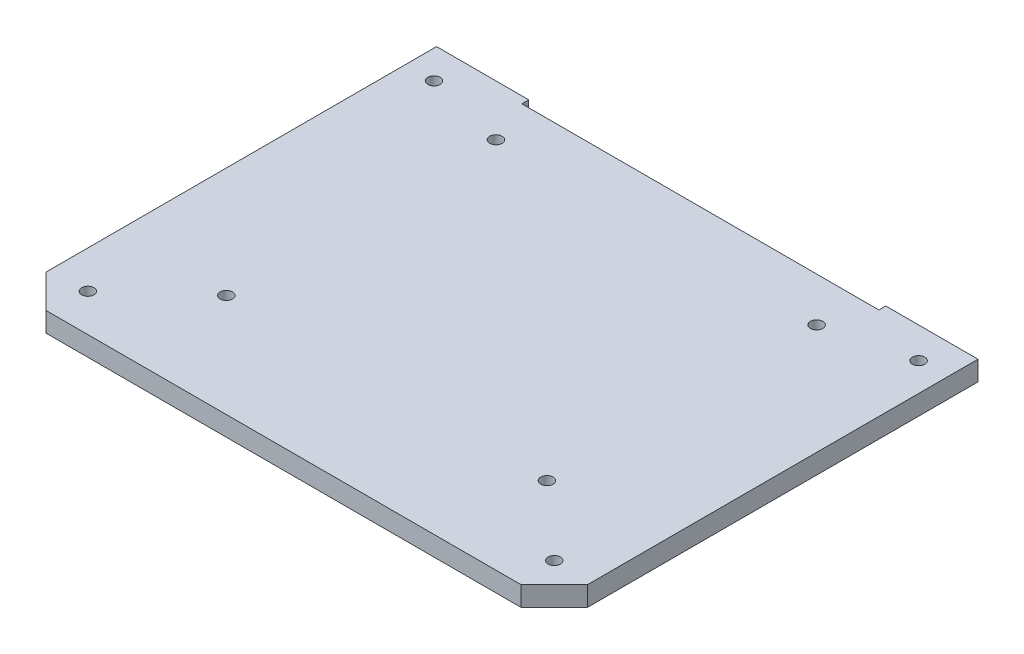
SolidWorks part; units mm, degrees
ref_plane "Front Plane" through (0, 0, 0) normal (0, 0, 1) x (1, 0, 0)
ref_plane "Top Plane" through (0, 0, 0) normal (0, 1, 0) x (1, 0, 0)
ref_plane "Right Plane" through (0, 0, 0) normal (1, 0, 0) x (0, 0, -1)
ref_plane "PZ26" through (0, 26, 0) normal (0, 1, 0) x (1, 0, 0)
sketch "Sketch1" plane through (0, 26, 0) normal (0, 1, 0) x (1, 0, 0)
  line L0 (-65.187, -126.3) -> (65.187, -126.3)
  line L1 (65.187, -126.3) -> (74.3, -117.187)
  line L2 (74.3, -117.187) -> (74.3, -11.9)
  line L3 (74.3, -11.9) -> (-74.3, -11.9)
  line L4 (-74.3, -11.9) -> (-74.3, -117.187)
  line L5 (-74.3, -117.187) -> (-65.187, -126.3)
extrude "Lid Plate" add sketch "Sketch1" along normal blind 2.4
ref_plane "PZ23" through (0, 23, 0) normal (0, 1, 0) x (1, 0, 0)
sketch "Sketch2" plane through (0, 23, 0) normal (0, 1, 0) x (1, 0, 0)
  line L0 (74.3, -11.9) -> (74.3, -117.187)
  line L1 (74.3, -117.187) -> (65.187, -126.3)
  line L2 (65.187, -126.3) -> (-65.187, -126.3)
  line L3 (-65.187, -126.3) -> (-74.3, -117.187)
  line L4 (-74.3, -117.187) -> (-74.3, -11.9)
  line L5 (-74.3, -11.9) -> (-72.7, -11.9)
  line L6 (-72.7, -11.9) -> (-72.7, -116.5243)
  line L7 (-72.7, -116.5243) -> (-64.5243, -124.7)
  line L8 (-64.5243, -124.7) -> (64.5243, -124.7)
  line L9 (64.5243, -124.7) -> (72.7, -116.5243)
  line L10 (72.7, -116.5243) -> (72.7, -11.9)
  line L11 (72.7, -11.9) -> (74.3, -11.9)
extrude "Drip Skirt" add sketch "Sketch2" along normal blind 3.01
sketch "Sketch3" plane through (0, 23, 0) normal (0, 1, 0) x (1, 0, 0)
  line L0 (-74.3, -11.9) -> (-49, -11.9)
  line L1 (-49, -11.9) -> (-49, -10)
  line L2 (-49, -10) -> (-74.3, -10)
  line L3 (-74.3, -10) -> (-74.3, -11.9)
extrude "Front Skirt L" add sketch "Sketch3" along normal blind 5.4
sketch "Sketch4" plane through (0, 23, 0) normal (0, 1, 0) x (1, 0, 0)
  line L0 (49, -11.9) -> (74.3, -11.9)
  line L1 (74.3, -11.9) -> (74.3, -10)
  line L2 (74.3, -10) -> (49, -10)
  line L3 (49, -10) -> (49, -11.9)
extrude "Front Skirt R" add sketch "Sketch4" along normal blind 5.4
ref_plane "PZ25" through (0, 25, 0) normal (0, 1, 0) x (1, 0, 0)
sketch "Sketch5" plane through (0, 25, 0) normal (0, 1, 0) x (1, 0, 0)
  circle A0 centre (-66.5, -18.5) radius 1.7
  circle A1 centre (66.5, -18.5) radius 1.7
  circle A2 centre (-64, -116) radius 1.7
  circle A3 centre (64, -116) radius 1.7
  circle A4 centre (-44, -24) radius 1.7
  circle A5 centre (-44, -98) radius 1.7
  circle A6 centre (44, -24) radius 1.7
  circle A7 centre (44, -98) radius 1.7
extrude "Screw Holes" cut sketch "Sketch5" along normal blind 4.4
equation "\"BOARD_REAR\" = 86.0"
equation "\"BOARD_FRONT\" = 41.0"
equation "\"BOARD_END\" = 22.0"
equation "\"BOARD_ANGLED\" = 30.0"
equation "\"BOARD_DEPTH\" = 41.8431"
equation "\"PCB_T\" = 1.6"
equation "\"ABOVE_PCB\" = 14.0"
equation "\"BELOW_PCB\" = 6.0"
equation "\"MID_PARTS_H\" = 9.0"
equation "\"BOARD_HOLE_PILOT\" = 1.6"
equation "\"J2_X\" = 19.0"
equation "\"DUPONT_DROP\" = 14.0"
equation "\"BEND_R\" = 5.0"
equation "\"BOARD_GAP\" = 3.0"
equation "\"TOF_FOV\" = 25.0"
equation "\"TOF_MARGIN_DEG\" = 5.0"
equation "\"TOF_WIN_MARGIN\" = 1.0"
equation "\"TOF_Z\" = 9.0"
equation "\"TOF_SIDE_BEARING\" = 90.0"
equation "\"TOF_CONE_LEN\" = 70.0"
equation "\"CAM_W\" = 29.2"
equation "\"CAM_H\" = 28.2"
equation "\"CAM_D\" = 12.35"
equation "\"CAM_FRONT_Y\" = 43.0"
equation "\"CAM_BOTTOM_Z\" = 17.0"
equation "\"CAM_LENS_UP\" = 11.6"
equation "\"CAM_LENS_OPEN\" = 9.6"
equation "\"CAM_HFOV\" = 53.5"
equation "\"CAM_VFOV\" = 41.41"
equation "\"CAM_FOV_MARGIN\" = 3.0"
equation "\"CAM_FIT\" = 0.3"
equation "\"RIBBON_W\" = 16.0"
equation "\"RIBBON_T\" = 0.3"
equation "\"RIBBON_LEN\" = 150.0"
equation "\"RIBBON_EXIT_Y\" = 35.0"
equation "\"WALL\" = 2.4"
equation "\"HEAD_X\" = 48.4"
equation "\"HEAD_REAR_Y\" = -11.9"
equation "\"CAM_FOAM\" = 2.8"
equation "\"HEAD_FRONT_Y\" = 48.2"
equation "\"HEAD_TOP_Z\" = 50.6"
equation "\"HEAD_BOT_Z\" = -28.4"
equation "\"HEAD_SPLIT_Z\" = -4.0"
equation "\"SKIRT_T\" = 1.2"
equation "\"SKIRT_H\" = 3.0"
equation "\"SKIRT_FIT\" = 0.3"
equation "\"VISOR\" = 7.8"
equation "\"VISOR_Z\" = 40.0"
equation "\"ROOF_SLOPE_Y\" = 40.0"
equation "\"ROOF_CHAMFER\" = 10.0"
equation "\"REAR_CHAMFER\" = 10.0"
equation "\"CORNER_CHAMFER\" = 6.0"
equation "\"LOWER_SIDE_FACET\" = 6.0"
equation "\"LIGHTBAR_DEPTH\" = 1.0"
equation "\"HOOD_Z\" = 14.0"
equation "\"HOOD_L\" = 6.0"
equation "\"SIDE_HOOD_L\" = 4.0"
equation "\"INSERT_M3_D\" = 4.0"
equation "\"INSERT_M3_L\" = 6.0"
equation "\"M3_CLEAR\" = 3.4"
equation "\"M2_PILOT\" = 1.6"
equation "\"M25_PILOT\" = 2.2"
equation "\"BOX_X\" = 72.4"
equation "\"BOX_FRONT_Y\" = -11.9"
equation "\"BOX_REAR_Y\" = -124.4"
equation "\"BOX_BOT_Z\" = -28.4"
equation "\"BOX_TOP_Z\" = 26.0"
equation "\"LID_T\" = 2.4"
equation "\"LID_SKIRT\" = 1.6"
equation "\"LID_TONGUE_H\" = 3.0"
equation "\"LID_FIT\" = 0.3"
equation "\"PI_STANDOFF\" = 8.0"
equation "\"BOX_REAR_CHAMFER\" = 8.0"
equation "\"BOX_REAR_FACET\" = 4.0"
equation "\"VENT_UPSTAND\" = 3.0"
equation "\"TUBE_D\" = 22.2"
equation "\"TUBE_LINER\" = 1.0"
equation "\"MOUNT_Y\" = -70.0"
equation "\"RAIL_W\" = 30.0"
equation "\"RAIL_W2\" = 38.0"
equation "\"RAIL_H\" = 6.0"
equation "\"SLIDE\" = 0.3"
equation "\"STOP_T\" = 6.0"
equation "\"CLAMP_W\" = 40.0"
equation "\"CLAMP_HALF\" = 20.0"
equation "\"CLAMP_DROP\" = 12.0"
equation "\"CAP_T\" = 12.0"
equation "\"CLAMP_BOLT_OFF\" = 16.6"
equation "\"M5_INSERT_D\" = 6.4"
equation "\"M5_CLEAR\" = 5.5"
equation "\"LOCK_D\" = 3.3"
equation "\"POD_TILT_DEG\" = 0.0"
equation "\"PRINT_LIMIT\" = 180.0"
equation "\"PI5_L\" = 85.0"
equation "\"PI5_W\" = 56.0"
equation "\"PI5_T\" = 1.6"
equation "\"PI5_USBC_BX\" = 11.2"
equation "\"PI5_ETH_BY\" = 10.2"
equation "\"PI5_PORT_OVERHANG\" = 3.0"
equation "\"PI5_FPC_H\" = 5.0"
equation "\"PI5_FPC_USE\" = 0.0"
equation "\"PI5_PIN1_BX\" = 8.37"
equation "\"HEADER_BASE_H\" = 2.5"
equation "\"DUPONT_L\" = 14.0"
equation "\"PI5_UNDERSIDE\" = 1.5"
equation "\"COOLER_H\" = 15.0"
equation "\"HAT_W\" = 65.0"
equation "\"HAT_D\" = 56.5"
equation "\"HAT_T\" = 1.6"
equation "\"HAT_SPACER\" = 16.0"
equation "\"HAILO_H\" = 10.0"
equation "\"STACK_PINS_H\" = 6.0"
equation "\"DUPONT_SEAT\" = 0.5"
equation "\"PCIE_FFC_LOOP\" = 6.0"
equation "\"HAILO_AIR_GAP_MIN\" = 8.0"
equation "\"M25_CLEAR\" = 2.7"
equation "\"PI_X0\" = -55.0"
equation "\"PI_Y1\" = -36.5"
equation "\"PI_Y0\" = -92.5"
equation "\"BOX_LEN\" = 112.5"
equation "\"COVER_T\" = 3.0"
equation "\"COVER_TOP_Z\" = 6.5"
equation "\"SIDE_LEDGE_Z\" = -2.5"
equation "\"UPPER_LEDGE_Z\" = 15.5"
equation "\"REAR_LEDGE_Z\" = 8.0"
equation "\"LEDGE_L\" = 4.0"
equation "\"RIBBON_W_PI\" = 11.5"
equation "\"RIBBON_RUN_Z\" = 12.0"
equation "\"RIBBON_SPEC_LEN\" = 200.0"
